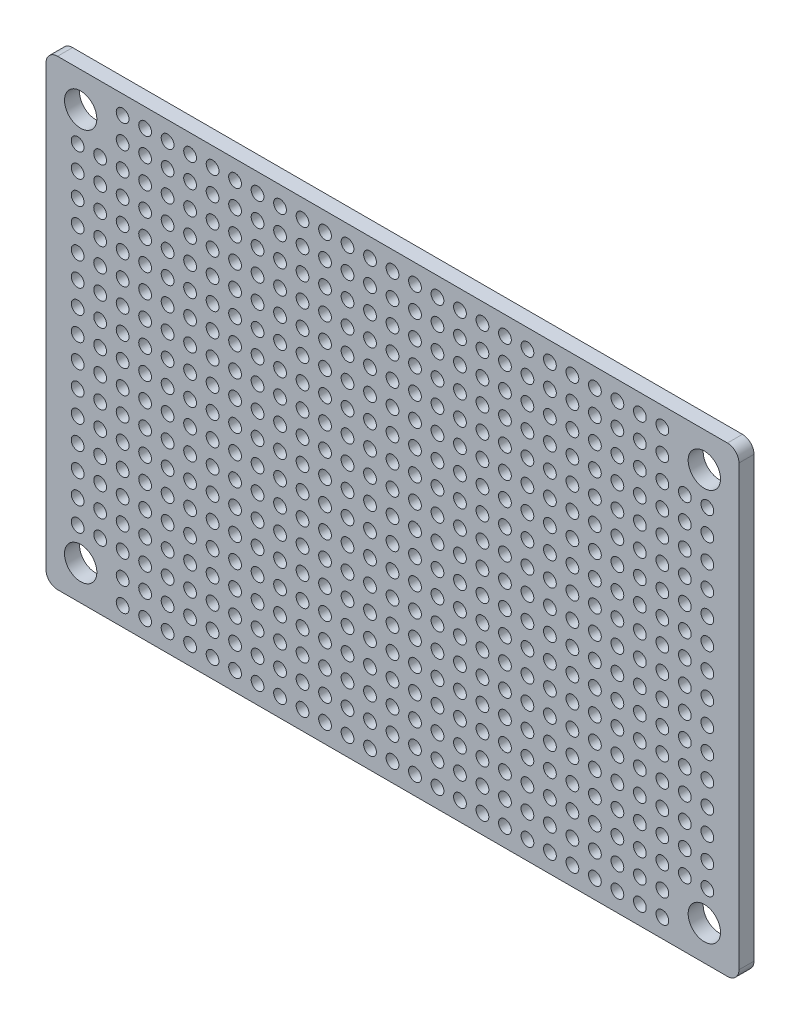
SolidWorks part; units mm, degrees
ref_plane "Front Plane" through (0, 0, 0) normal (0, 0, 1) x (1, 0, 0)
ref_plane "Top Plane" through (0, 0, 0) normal (0, 1, 0) x (1, 0, 0)
ref_plane "Right Plane" through (0, 0, 0) normal (1, 0, 0) x (0, 0, -1)
sketch "Sketch1" plane through (0, 0, 0) normal (0, 0, 1) x (1, 0, 0)
  line L0 (0, 25.4) -> (76.2, 25.4) construction
  line L1 (0, 0) -> (76.2, 0)
  line L2 (0, 0) -> (0, 50.8)
  line L3 (0, 50.8) -> (76.2, 50.8)
  line L4 (76.2, 0) -> (76.2, 50.8)
  line L5 (38.1, 50.8) -> (38.1, 0) construction
  line L6 (4.1421, 48.7367) -> (72.0579, 48.7367) construction
  line L7 (72.39, 2.0633) -> (72.39, 48.7367) construction
  circle A0 centre (3.81, 46.99) radius 1.778
  circle A1 centre (72.39, 46.99) radius 1.778
  circle A2 centre (3.81, 3.81) radius 1.778
  circle A3 centre (72.39, 3.81) radius 1.778
  circle A6 centre (8.4239, 48.7367) radius 0.702
  circle A7 centre (10.8969, 48.7367) radius 0.702
  circle A8 centre (13.3699, 48.7367) radius 0.702
  circle A9 centre (15.8429, 48.7367) radius 0.702
  circle A10 centre (18.3159, 48.7367) radius 0.702
  circle A11 centre (20.7889, 48.7367) radius 0.702
  circle A12 centre (23.2619, 48.7367) radius 0.702
  circle A13 centre (25.7349, 48.7367) radius 0.702
  circle A14 centre (28.208, 48.7367) radius 0.702
  circle A15 centre (30.681, 48.7367) radius 0.702
  circle A16 centre (33.154, 48.7367) radius 0.702
  circle A17 centre (35.627, 48.7367) radius 0.702
  circle A18 centre (38.1, 48.7367) radius 0.702
  circle A19 centre (40.573, 48.7367) radius 0.702
  circle A20 centre (43.046, 48.7367) radius 0.702
  circle A21 centre (45.519, 48.7367) radius 0.702
  circle A22 centre (47.992, 48.7367) radius 0.702
  circle A23 centre (50.4651, 48.7367) radius 0.702
  circle A24 centre (52.9381, 48.7367) radius 0.702
  circle A25 centre (55.4111, 48.7367) radius 0.702
  circle A26 centre (57.8841, 48.7367) radius 0.702
  circle A27 centre (60.3571, 48.7367) radius 0.702
  circle A28 centre (62.8301, 48.7367) radius 0.702
  circle A29 centre (65.3031, 48.7367) radius 0.702
  circle A30 centre (67.7761, 48.7367) radius 0.702
  circle A35 centre (8.4239, 46.1437) radius 0.702
  circle A36 centre (10.8969, 46.1437) radius 0.702
  circle A37 centre (13.3699, 46.1437) radius 0.702
  circle A38 centre (15.8429, 46.1437) radius 0.702
  circle A39 centre (18.3159, 46.1437) radius 0.702
  circle A40 centre (20.7889, 46.1437) radius 0.702
  circle A41 centre (23.2619, 46.1437) radius 0.702
  circle A42 centre (25.7349, 46.1437) radius 0.702
  circle A43 centre (28.208, 46.1437) radius 0.702
  circle A44 centre (30.681, 46.1437) radius 0.702
  circle A45 centre (33.154, 46.1437) radius 0.702
  circle A46 centre (35.627, 46.1437) radius 0.702
  circle A47 centre (38.1, 46.1437) radius 0.702
  circle A48 centre (40.573, 46.1437) radius 0.702
  circle A49 centre (43.046, 46.1437) radius 0.702
  circle A50 centre (45.519, 46.1437) radius 0.702
  circle A51 centre (47.992, 46.1437) radius 0.702
  circle A52 centre (50.4651, 46.1437) radius 0.702
  circle A53 centre (52.9381, 46.1437) radius 0.702
  circle A54 centre (55.4111, 46.1437) radius 0.702
  circle A55 centre (57.8841, 46.1437) radius 0.702
  circle A56 centre (60.3571, 46.1437) radius 0.702
  circle A57 centre (62.8301, 46.1437) radius 0.702
  circle A58 centre (65.3031, 46.1437) radius 0.702
  circle A59 centre (67.7761, 46.1437) radius 0.702
  circle A62 centre (3.4779, 43.5508) radius 0.702
  circle A63 centre (5.9509, 43.5508) radius 0.702
  circle A64 centre (8.4239, 43.5508) radius 0.702
  circle A65 centre (10.8969, 43.5508) radius 0.702
  circle A66 centre (13.3699, 43.5508) radius 0.702
  circle A67 centre (15.8429, 43.5508) radius 0.702
  circle A68 centre (18.3159, 43.5508) radius 0.702
  circle A69 centre (20.7889, 43.5508) radius 0.702
  circle A70 centre (23.2619, 43.5508) radius 0.702
  circle A71 centre (25.7349, 43.5508) radius 0.702
  circle A72 centre (28.208, 43.5508) radius 0.702
  circle A73 centre (30.681, 43.5508) radius 0.702
  circle A74 centre (33.154, 43.5508) radius 0.702
  circle A75 centre (35.627, 43.5508) radius 0.702
  circle A76 centre (38.1, 43.5508) radius 0.702
  circle A77 centre (40.573, 43.5508) radius 0.702
  circle A78 centre (43.046, 43.5508) radius 0.702
  circle A79 centre (45.519, 43.5508) radius 0.702
  circle A80 centre (47.992, 43.5508) radius 0.702
  circle A81 centre (50.4651, 43.5508) radius 0.702
  circle A82 centre (52.9381, 43.5508) radius 0.702
  circle A83 centre (55.4111, 43.5508) radius 0.702
  circle A84 centre (57.8841, 43.5508) radius 0.702
  circle A85 centre (60.3571, 43.5508) radius 0.702
  circle A86 centre (62.8301, 43.5508) radius 0.702
  circle A87 centre (65.3031, 43.5508) radius 0.702
  circle A88 centre (67.7761, 43.5508) radius 0.702
  circle A89 centre (70.2491, 43.5508) radius 0.702
  circle A90 centre (72.7221, 43.5508) radius 0.702
  circle A91 centre (3.4779, 40.9578) radius 0.702
  circle A92 centre (5.9509, 40.9578) radius 0.702
  circle A93 centre (8.4239, 40.9578) radius 0.702
  circle A94 centre (10.8969, 40.9578) radius 0.702
  circle A95 centre (13.3699, 40.9578) radius 0.702
  circle A96 centre (15.8429, 40.9578) radius 0.702
  circle A97 centre (18.3159, 40.9578) radius 0.702
  circle A98 centre (20.7889, 40.9578) radius 0.702
  circle A99 centre (23.2619, 40.9578) radius 0.702
  circle A100 centre (25.7349, 40.9578) radius 0.702
  circle A101 centre (28.208, 40.9578) radius 0.702
  circle A102 centre (30.681, 40.9578) radius 0.702
  circle A103 centre (33.154, 40.9578) radius 0.702
  circle A104 centre (35.627, 40.9578) radius 0.702
  circle A105 centre (38.1, 40.9578) radius 0.702
  circle A106 centre (40.573, 40.9578) radius 0.702
  circle A107 centre (43.046, 40.9578) radius 0.702
  circle A108 centre (45.519, 40.9578) radius 0.702
  circle A109 centre (47.992, 40.9578) radius 0.702
  circle A110 centre (50.4651, 40.9578) radius 0.702
  circle A111 centre (52.9381, 40.9578) radius 0.702
  circle A112 centre (55.4111, 40.9578) radius 0.702
  circle A113 centre (57.8841, 40.9578) radius 0.702
  circle A114 centre (60.3571, 40.9578) radius 0.702
  circle A115 centre (62.8301, 40.9578) radius 0.702
  circle A116 centre (65.3031, 40.9578) radius 0.702
  circle A117 centre (67.7761, 40.9578) radius 0.702
  circle A118 centre (70.2491, 40.9578) radius 0.702
  circle A119 centre (72.7221, 40.9578) radius 0.702
  circle A120 centre (3.4779, 38.3648) radius 0.702
  circle A121 centre (5.9509, 38.3648) radius 0.702
  circle A122 centre (8.4239, 38.3648) radius 0.702
  circle A123 centre (10.8969, 38.3648) radius 0.702
  circle A124 centre (13.3699, 38.3648) radius 0.702
  circle A125 centre (15.8429, 38.3648) radius 0.702
  circle A126 centre (18.3159, 38.3648) radius 0.702
  circle A127 centre (20.7889, 38.3648) radius 0.702
  circle A128 centre (23.2619, 38.3648) radius 0.702
  circle A129 centre (25.7349, 38.3648) radius 0.702
  circle A130 centre (28.208, 38.3648) radius 0.702
  circle A131 centre (30.681, 38.3648) radius 0.702
  circle A132 centre (33.154, 38.3648) radius 0.702
  circle A133 centre (35.627, 38.3648) radius 0.702
  circle A134 centre (38.1, 38.3648) radius 0.702
  circle A135 centre (40.573, 38.3648) radius 0.702
  circle A136 centre (43.046, 38.3648) radius 0.702
  circle A137 centre (45.519, 38.3648) radius 0.702
  circle A138 centre (47.992, 38.3648) radius 0.702
  circle A139 centre (50.4651, 38.3648) radius 0.702
  circle A140 centre (52.9381, 38.3648) radius 0.702
  circle A141 centre (55.4111, 38.3648) radius 0.702
  circle A142 centre (57.8841, 38.3648) radius 0.702
  circle A143 centre (60.3571, 38.3648) radius 0.702
  circle A144 centre (62.8301, 38.3648) radius 0.702
  circle A145 centre (65.3031, 38.3648) radius 0.702
  circle A146 centre (67.7761, 38.3648) radius 0.702
  circle A147 centre (70.2491, 38.3648) radius 0.702
  circle A148 centre (72.7221, 38.3648) radius 0.702
  circle A149 centre (3.4779, 35.7719) radius 0.702
  circle A150 centre (5.9509, 35.7719) radius 0.702
  circle A151 centre (8.4239, 35.7719) radius 0.702
  circle A152 centre (10.8969, 35.7719) radius 0.702
  circle A153 centre (13.3699, 35.7719) radius 0.702
  circle A154 centre (15.8429, 35.7719) radius 0.702
  circle A155 centre (18.3159, 35.7719) radius 0.702
  circle A156 centre (20.7889, 35.7719) radius 0.702
  circle A157 centre (23.2619, 35.7719) radius 0.702
  circle A158 centre (25.7349, 35.7719) radius 0.702
  circle A159 centre (28.208, 35.7719) radius 0.702
  circle A160 centre (30.681, 35.7719) radius 0.702
  circle A161 centre (33.154, 35.7719) radius 0.702
  circle A162 centre (35.627, 35.7719) radius 0.702
  circle A163 centre (38.1, 35.7719) radius 0.702
  circle A164 centre (40.573, 35.7719) radius 0.702
  circle A165 centre (43.046, 35.7719) radius 0.702
  circle A166 centre (45.519, 35.7719) radius 0.702
  circle A167 centre (47.992, 35.7719) radius 0.702
  circle A168 centre (50.4651, 35.7719) radius 0.702
  circle A169 centre (52.9381, 35.7719) radius 0.702
  circle A170 centre (55.4111, 35.7719) radius 0.702
  circle A171 centre (57.8841, 35.7719) radius 0.702
  circle A172 centre (60.3571, 35.7719) radius 0.702
  circle A173 centre (62.8301, 35.7719) radius 0.702
  circle A174 centre (65.3031, 35.7719) radius 0.702
  circle A175 centre (67.7761, 35.7719) radius 0.702
  circle A176 centre (70.2491, 35.7719) radius 0.702
  circle A177 centre (72.7221, 35.7719) radius 0.702
  circle A178 centre (3.4779, 33.1789) radius 0.702
  circle A179 centre (5.9509, 33.1789) radius 0.702
  circle A180 centre (8.4239, 33.1789) radius 0.702
  circle A181 centre (10.8969, 33.1789) radius 0.702
  circle A182 centre (13.3699, 33.1789) radius 0.702
  circle A183 centre (15.8429, 33.1789) radius 0.702
  circle A184 centre (18.3159, 33.1789) radius 0.702
  circle A185 centre (20.7889, 33.1789) radius 0.702
  circle A186 centre (23.2619, 33.1789) radius 0.702
  circle A187 centre (25.7349, 33.1789) radius 0.702
  circle A188 centre (28.208, 33.1789) radius 0.702
  circle A189 centre (30.681, 33.1789) radius 0.702
  circle A190 centre (33.154, 33.1789) radius 0.702
  circle A191 centre (35.627, 33.1789) radius 0.702
  circle A192 centre (38.1, 33.1789) radius 0.702
  circle A193 centre (40.573, 33.1789) radius 0.702
  circle A194 centre (43.046, 33.1789) radius 0.702
  circle A195 centre (45.519, 33.1789) radius 0.702
  circle A196 centre (47.992, 33.1789) radius 0.702
  circle A197 centre (50.4651, 33.1789) radius 0.702
  circle A198 centre (52.9381, 33.1789) radius 0.702
  circle A199 centre (55.4111, 33.1789) radius 0.702
  circle A200 centre (57.8841, 33.1789) radius 0.702
  circle A201 centre (60.3571, 33.1789) radius 0.702
  circle A202 centre (62.8301, 33.1789) radius 0.702
  circle A203 centre (65.3031, 33.1789) radius 0.702
  circle A204 centre (67.7761, 33.1789) radius 0.702
  circle A205 centre (70.2491, 33.1789) radius 0.702
  circle A206 centre (72.7221, 33.1789) radius 0.702
  circle A207 centre (3.4779, 30.5859) radius 0.702
  circle A208 centre (5.9509, 30.5859) radius 0.702
  circle A209 centre (8.4239, 30.5859) radius 0.702
  circle A210 centre (10.8969, 30.5859) radius 0.702
  circle A211 centre (13.3699, 30.5859) radius 0.702
  circle A212 centre (15.8429, 30.5859) radius 0.702
  circle A213 centre (18.3159, 30.5859) radius 0.702
  circle A214 centre (20.7889, 30.5859) radius 0.702
  circle A215 centre (23.2619, 30.5859) radius 0.702
  circle A216 centre (25.7349, 30.5859) radius 0.702
  circle A217 centre (28.208, 30.5859) radius 0.702
  circle A218 centre (30.681, 30.5859) radius 0.702
  circle A219 centre (33.154, 30.5859) radius 0.702
  circle A220 centre (35.627, 30.5859) radius 0.702
  circle A221 centre (38.1, 30.5859) radius 0.702
  circle A222 centre (40.573, 30.5859) radius 0.702
  circle A223 centre (43.046, 30.5859) radius 0.702
  circle A224 centre (45.519, 30.5859) radius 0.702
  circle A225 centre (47.992, 30.5859) radius 0.702
  circle A226 centre (50.4651, 30.5859) radius 0.702
  circle A227 centre (52.9381, 30.5859) radius 0.702
  circle A228 centre (55.4111, 30.5859) radius 0.702
  circle A229 centre (57.8841, 30.5859) radius 0.702
  circle A230 centre (60.3571, 30.5859) radius 0.702
  circle A231 centre (62.8301, 30.5859) radius 0.702
  circle A232 centre (65.3031, 30.5859) radius 0.702
  circle A233 centre (67.7761, 30.5859) radius 0.702
  circle A234 centre (70.2491, 30.5859) radius 0.702
  circle A235 centre (72.7221, 30.5859) radius 0.702
  circle A236 centre (3.4779, 27.993) radius 0.702
  circle A237 centre (5.9509, 27.993) radius 0.702
  circle A238 centre (8.4239, 27.993) radius 0.702
  circle A239 centre (10.8969, 27.993) radius 0.702
  circle A240 centre (13.3699, 27.993) radius 0.702
  circle A241 centre (15.8429, 27.993) radius 0.702
  circle A242 centre (18.3159, 27.993) radius 0.702
  circle A243 centre (20.7889, 27.993) radius 0.702
  circle A244 centre (23.2619, 27.993) radius 0.702
  circle A245 centre (25.7349, 27.993) radius 0.702
  circle A246 centre (28.208, 27.993) radius 0.702
  circle A247 centre (30.681, 27.993) radius 0.702
  circle A248 centre (33.154, 27.993) radius 0.702
  circle A249 centre (35.627, 27.993) radius 0.702
  circle A250 centre (38.1, 27.993) radius 0.702
  circle A251 centre (40.573, 27.993) radius 0.702
  circle A252 centre (43.046, 27.993) radius 0.702
  circle A253 centre (45.519, 27.993) radius 0.702
  circle A254 centre (47.992, 27.993) radius 0.702
  circle A255 centre (50.4651, 27.993) radius 0.702
  circle A256 centre (52.9381, 27.993) radius 0.702
  circle A257 centre (55.4111, 27.993) radius 0.702
  circle A258 centre (57.8841, 27.993) radius 0.702
  circle A259 centre (60.3571, 27.993) radius 0.702
  circle A260 centre (62.8301, 27.993) radius 0.702
  circle A261 centre (65.3031, 27.993) radius 0.702
  circle A262 centre (67.7761, 27.993) radius 0.702
  circle A263 centre (70.2491, 27.993) radius 0.702
  circle A264 centre (72.7221, 27.993) radius 0.702
  circle A265 centre (3.4779, 25.4) radius 0.702
  circle A266 centre (5.9509, 25.4) radius 0.702
  circle A267 centre (8.4239, 25.4) radius 0.702
  circle A268 centre (10.8969, 25.4) radius 0.702
  circle A269 centre (13.3699, 25.4) radius 0.702
  circle A270 centre (15.8429, 25.4) radius 0.702
  circle A271 centre (18.3159, 25.4) radius 0.702
  circle A272 centre (20.7889, 25.4) radius 0.702
  circle A273 centre (23.2619, 25.4) radius 0.702
  circle A274 centre (25.7349, 25.4) radius 0.702
  circle A275 centre (28.208, 25.4) radius 0.702
  circle A276 centre (30.681, 25.4) radius 0.702
  circle A277 centre (33.154, 25.4) radius 0.702
  circle A278 centre (35.627, 25.4) radius 0.702
  circle A279 centre (38.1, 25.4) radius 0.702
  circle A280 centre (40.573, 25.4) radius 0.702
  circle A281 centre (43.046, 25.4) radius 0.702
  circle A282 centre (45.519, 25.4) radius 0.702
  circle A283 centre (47.992, 25.4) radius 0.702
  circle A284 centre (50.4651, 25.4) radius 0.702
  circle A285 centre (52.9381, 25.4) radius 0.702
  circle A286 centre (55.4111, 25.4) radius 0.702
  circle A287 centre (57.8841, 25.4) radius 0.702
  circle A288 centre (60.3571, 25.4) radius 0.702
  circle A289 centre (62.8301, 25.4) radius 0.702
  circle A290 centre (65.3031, 25.4) radius 0.702
  circle A291 centre (67.7761, 25.4) radius 0.702
  circle A292 centre (70.2491, 25.4) radius 0.702
  circle A293 centre (72.7221, 25.4) radius 0.702
  circle A294 centre (3.4779, 22.807) radius 0.702
  circle A295 centre (5.9509, 22.807) radius 0.702
  circle A296 centre (8.4239, 22.807) radius 0.702
  circle A297 centre (10.8969, 22.807) radius 0.702
  circle A298 centre (13.3699, 22.807) radius 0.702
  circle A299 centre (15.8429, 22.807) radius 0.702
  circle A300 centre (18.3159, 22.807) radius 0.702
  circle A301 centre (20.7889, 22.807) radius 0.702
  circle A302 centre (23.2619, 22.807) radius 0.702
  circle A303 centre (25.7349, 22.807) radius 0.702
  circle A304 centre (28.208, 22.807) radius 0.702
  circle A305 centre (30.681, 22.807) radius 0.702
  circle A306 centre (33.154, 22.807) radius 0.702
  circle A307 centre (35.627, 22.807) radius 0.702
  circle A308 centre (38.1, 22.807) radius 0.702
  circle A309 centre (40.573, 22.807) radius 0.702
  circle A310 centre (43.046, 22.807) radius 0.702
  circle A311 centre (45.519, 22.807) radius 0.702
  circle A312 centre (47.992, 22.807) radius 0.702
  circle A313 centre (50.4651, 22.807) radius 0.702
  circle A314 centre (52.9381, 22.807) radius 0.702
  circle A315 centre (55.4111, 22.807) radius 0.702
  circle A316 centre (57.8841, 22.807) radius 0.702
  circle A317 centre (60.3571, 22.807) radius 0.702
  circle A318 centre (62.8301, 22.807) radius 0.702
  circle A319 centre (65.3031, 22.807) radius 0.702
  circle A320 centre (67.7761, 22.807) radius 0.702
  circle A321 centre (70.2491, 22.807) radius 0.702
  circle A322 centre (72.7221, 22.807) radius 0.702
  circle A323 centre (3.4779, 20.2141) radius 0.702
  circle A324 centre (5.9509, 20.2141) radius 0.702
  circle A325 centre (8.4239, 20.2141) radius 0.702
  circle A326 centre (10.8969, 20.2141) radius 0.702
  circle A327 centre (13.3699, 20.2141) radius 0.702
  circle A328 centre (15.8429, 20.2141) radius 0.702
  circle A329 centre (18.3159, 20.2141) radius 0.702
  circle A330 centre (20.7889, 20.2141) radius 0.702
  circle A331 centre (23.2619, 20.2141) radius 0.702
  circle A332 centre (25.7349, 20.2141) radius 0.702
  circle A333 centre (28.208, 20.2141) radius 0.702
  circle A334 centre (30.681, 20.2141) radius 0.702
  circle A335 centre (33.154, 20.2141) radius 0.702
  circle A336 centre (35.627, 20.2141) radius 0.702
  circle A337 centre (38.1, 20.2141) radius 0.702
  circle A338 centre (40.573, 20.2141) radius 0.702
  circle A339 centre (43.046, 20.2141) radius 0.702
  circle A340 centre (45.519, 20.2141) radius 0.702
  circle A341 centre (47.992, 20.2141) radius 0.702
  circle A342 centre (50.4651, 20.2141) radius 0.702
  circle A343 centre (52.9381, 20.2141) radius 0.702
  circle A344 centre (55.4111, 20.2141) radius 0.702
  circle A345 centre (57.8841, 20.2141) radius 0.702
  circle A346 centre (60.3571, 20.2141) radius 0.702
  circle A347 centre (62.8301, 20.2141) radius 0.702
  circle A348 centre (65.3031, 20.2141) radius 0.702
  circle A349 centre (67.7761, 20.2141) radius 0.702
  circle A350 centre (70.2491, 20.2141) radius 0.702
  circle A351 centre (72.7221, 20.2141) radius 0.702
  circle A352 centre (3.4779, 17.6211) radius 0.702
  circle A353 centre (5.9509, 17.6211) radius 0.702
  circle A354 centre (8.4239, 17.6211) radius 0.702
  circle A355 centre (10.8969, 17.6211) radius 0.702
  circle A356 centre (13.3699, 17.6211) radius 0.702
  circle A357 centre (15.8429, 17.6211) radius 0.702
  circle A358 centre (18.3159, 17.6211) radius 0.702
  circle A359 centre (20.7889, 17.6211) radius 0.702
  circle A360 centre (23.2619, 17.6211) radius 0.702
  circle A361 centre (25.7349, 17.6211) radius 0.702
  circle A362 centre (28.208, 17.6211) radius 0.702
  circle A363 centre (30.681, 17.6211) radius 0.702
  circle A364 centre (33.154, 17.6211) radius 0.702
  circle A365 centre (35.627, 17.6211) radius 0.702
  circle A366 centre (38.1, 17.6211) radius 0.702
  circle A367 centre (40.573, 17.6211) radius 0.702
  circle A368 centre (43.046, 17.6211) radius 0.702
  circle A369 centre (45.519, 17.6211) radius 0.702
  circle A370 centre (47.992, 17.6211) radius 0.702
  circle A371 centre (50.4651, 17.6211) radius 0.702
  circle A372 centre (52.9381, 17.6211) radius 0.702
  circle A373 centre (55.4111, 17.6211) radius 0.702
  circle A374 centre (57.8841, 17.6211) radius 0.702
  circle A375 centre (60.3571, 17.6211) radius 0.702
  circle A376 centre (62.8301, 17.6211) radius 0.702
  circle A377 centre (65.3031, 17.6211) radius 0.702
  circle A378 centre (67.7761, 17.6211) radius 0.702
  circle A379 centre (70.2491, 17.6211) radius 0.702
  circle A380 centre (72.7221, 17.6211) radius 0.702
  circle A381 centre (3.4779, 15.0281) radius 0.702
  circle A382 centre (5.9509, 15.0281) radius 0.702
  circle A383 centre (8.4239, 15.0281) radius 0.702
  circle A384 centre (10.8969, 15.0281) radius 0.702
  circle A385 centre (13.3699, 15.0281) radius 0.702
  circle A386 centre (15.8429, 15.0281) radius 0.702
  circle A387 centre (18.3159, 15.0281) radius 0.702
  circle A388 centre (20.7889, 15.0281) radius 0.702
  circle A389 centre (23.2619, 15.0281) radius 0.702
  circle A390 centre (25.7349, 15.0281) radius 0.702
  circle A391 centre (28.208, 15.0281) radius 0.702
  circle A392 centre (30.681, 15.0281) radius 0.702
  circle A393 centre (33.154, 15.0281) radius 0.702
  circle A394 centre (35.627, 15.0281) radius 0.702
  circle A395 centre (38.1, 15.0281) radius 0.702
  circle A396 centre (40.573, 15.0281) radius 0.702
  circle A397 centre (43.046, 15.0281) radius 0.702
  circle A398 centre (45.519, 15.0281) radius 0.702
  circle A399 centre (47.992, 15.0281) radius 0.702
  circle A400 centre (50.4651, 15.0281) radius 0.702
  circle A401 centre (52.9381, 15.0281) radius 0.702
  circle A402 centre (55.4111, 15.0281) radius 0.702
  circle A403 centre (57.8841, 15.0281) radius 0.702
  circle A404 centre (60.3571, 15.0281) radius 0.702
  circle A405 centre (62.8301, 15.0281) radius 0.702
  circle A406 centre (65.3031, 15.0281) radius 0.702
  circle A407 centre (67.7761, 15.0281) radius 0.702
  circle A408 centre (70.2491, 15.0281) radius 0.702
  circle A409 centre (72.7221, 15.0281) radius 0.702
  circle A410 centre (3.4779, 12.4352) radius 0.702
  circle A411 centre (5.9509, 12.4352) radius 0.702
  circle A412 centre (8.4239, 12.4352) radius 0.702
  circle A413 centre (10.8969, 12.4352) radius 0.702
  circle A414 centre (13.3699, 12.4352) radius 0.702
  circle A415 centre (15.8429, 12.4352) radius 0.702
  circle A416 centre (18.3159, 12.4352) radius 0.702
  circle A417 centre (20.7889, 12.4352) radius 0.702
  circle A418 centre (23.2619, 12.4352) radius 0.702
  circle A419 centre (25.7349, 12.4352) radius 0.702
  circle A420 centre (28.208, 12.4352) radius 0.702
  circle A421 centre (30.681, 12.4352) radius 0.702
  circle A422 centre (33.154, 12.4352) radius 0.702
  circle A423 centre (35.627, 12.4352) radius 0.702
  circle A424 centre (38.1, 12.4352) radius 0.702
  circle A425 centre (40.573, 12.4352) radius 0.702
  circle A426 centre (43.046, 12.4352) radius 0.702
  circle A427 centre (45.519, 12.4352) radius 0.702
  circle A428 centre (47.992, 12.4352) radius 0.702
  circle A429 centre (50.4651, 12.4352) radius 0.702
  circle A430 centre (52.9381, 12.4352) radius 0.702
  circle A431 centre (55.4111, 12.4352) radius 0.702
  circle A432 centre (57.8841, 12.4352) radius 0.702
  circle A433 centre (60.3571, 12.4352) radius 0.702
  circle A434 centre (62.8301, 12.4352) radius 0.702
  circle A435 centre (65.3031, 12.4352) radius 0.702
  circle A436 centre (67.7761, 12.4352) radius 0.702
  circle A437 centre (70.2491, 12.4352) radius 0.702
  circle A438 centre (72.7221, 12.4352) radius 0.702
  circle A439 centre (3.4779, 9.8422) radius 0.702
  circle A440 centre (5.9509, 9.8422) radius 0.702
  circle A441 centre (8.4239, 9.8422) radius 0.702
  circle A442 centre (10.8969, 9.8422) radius 0.702
  circle A443 centre (13.3699, 9.8422) radius 0.702
  circle A444 centre (15.8429, 9.8422) radius 0.702
  circle A445 centre (18.3159, 9.8422) radius 0.702
  circle A446 centre (20.7889, 9.8422) radius 0.702
  circle A447 centre (23.2619, 9.8422) radius 0.702
  circle A448 centre (25.7349, 9.8422) radius 0.702
  circle A449 centre (28.208, 9.8422) radius 0.702
  circle A450 centre (30.681, 9.8422) radius 0.702
  circle A451 centre (33.154, 9.8422) radius 0.702
  circle A452 centre (35.627, 9.8422) radius 0.702
  circle A453 centre (38.1, 9.8422) radius 0.702
  circle A454 centre (40.573, 9.8422) radius 0.702
  circle A455 centre (43.046, 9.8422) radius 0.702
  circle A456 centre (45.519, 9.8422) radius 0.702
  circle A457 centre (47.992, 9.8422) radius 0.702
  circle A458 centre (50.4651, 9.8422) radius 0.702
  circle A459 centre (52.9381, 9.8422) radius 0.702
  circle A460 centre (55.4111, 9.8422) radius 0.702
  circle A461 centre (57.8841, 9.8422) radius 0.702
  circle A462 centre (60.3571, 9.8422) radius 0.702
  circle A463 centre (62.8301, 9.8422) radius 0.702
  circle A464 centre (65.3031, 9.8422) radius 0.702
  circle A465 centre (67.7761, 9.8422) radius 0.702
  circle A466 centre (70.2491, 9.8422) radius 0.702
  circle A467 centre (72.7221, 9.8422) radius 0.702
  circle A468 centre (3.4779, 7.2492) radius 0.702
  circle A469 centre (5.9509, 7.2492) radius 0.702
  circle A470 centre (8.4239, 7.2492) radius 0.702
  circle A471 centre (10.8969, 7.2492) radius 0.702
  circle A472 centre (13.3699, 7.2492) radius 0.702
  circle A473 centre (15.8429, 7.2492) radius 0.702
  circle A474 centre (18.3159, 7.2492) radius 0.702
  circle A475 centre (20.7889, 7.2492) radius 0.702
  circle A476 centre (23.2619, 7.2492) radius 0.702
  circle A477 centre (25.7349, 7.2492) radius 0.702
  circle A478 centre (28.208, 7.2492) radius 0.702
  circle A479 centre (30.681, 7.2492) radius 0.702
  circle A480 centre (33.154, 7.2492) radius 0.702
  circle A481 centre (35.627, 7.2492) radius 0.702
  circle A482 centre (38.1, 7.2492) radius 0.702
  circle A483 centre (40.573, 7.2492) radius 0.702
  circle A484 centre (43.046, 7.2492) radius 0.702
  circle A485 centre (45.519, 7.2492) radius 0.702
  circle A486 centre (47.992, 7.2492) radius 0.702
  circle A487 centre (50.4651, 7.2492) radius 0.702
  circle A488 centre (52.9381, 7.2492) radius 0.702
  circle A489 centre (55.4111, 7.2492) radius 0.702
  circle A490 centre (57.8841, 7.2492) radius 0.702
  circle A491 centre (60.3571, 7.2492) radius 0.702
  circle A492 centre (62.8301, 7.2492) radius 0.702
  circle A493 centre (65.3031, 7.2492) radius 0.702
  circle A494 centre (67.7761, 7.2492) radius 0.702
  circle A495 centre (70.2491, 7.2492) radius 0.702
  circle A496 centre (72.7221, 7.2492) radius 0.702
  circle A499 centre (8.4239, 4.6563) radius 0.702
  circle A500 centre (10.8969, 4.6563) radius 0.702
  circle A501 centre (13.3699, 4.6563) radius 0.702
  circle A502 centre (15.8429, 4.6563) radius 0.702
  circle A503 centre (18.3159, 4.6563) radius 0.702
  circle A504 centre (20.7889, 4.6563) radius 0.702
  circle A505 centre (23.2619, 4.6563) radius 0.702
  circle A506 centre (25.7349, 4.6563) radius 0.702
  circle A507 centre (28.208, 4.6563) radius 0.702
  circle A508 centre (30.681, 4.6563) radius 0.702
  circle A509 centre (33.154, 4.6563) radius 0.702
  circle A510 centre (35.627, 4.6563) radius 0.702
  circle A511 centre (38.1, 4.6563) radius 0.702
  circle A512 centre (40.573, 4.6563) radius 0.702
  circle A513 centre (43.046, 4.6563) radius 0.702
  circle A514 centre (45.519, 4.6563) radius 0.702
  circle A515 centre (47.992, 4.6563) radius 0.702
  circle A516 centre (50.4651, 4.6563) radius 0.702
  circle A517 centre (52.9381, 4.6563) radius 0.702
  circle A518 centre (55.4111, 4.6563) radius 0.702
  circle A519 centre (57.8841, 4.6563) radius 0.702
  circle A520 centre (60.3571, 4.6563) radius 0.702
  circle A521 centre (62.8301, 4.6563) radius 0.702
  circle A522 centre (65.3031, 4.6563) radius 0.702
  circle A523 centre (67.7761, 4.6563) radius 0.702
  circle A528 centre (8.4239, 2.0633) radius 0.702
  circle A529 centre (10.8969, 2.0633) radius 0.702
  circle A530 centre (13.3699, 2.0633) radius 0.702
  circle A531 centre (15.8429, 2.0633) radius 0.702
  circle A532 centre (18.3159, 2.0633) radius 0.702
  circle A533 centre (20.7889, 2.0633) radius 0.702
  circle A534 centre (23.2619, 2.0633) radius 0.702
  circle A535 centre (25.7349, 2.0633) radius 0.702
  circle A536 centre (28.208, 2.0633) radius 0.702
  circle A537 centre (30.681, 2.0633) radius 0.702
  circle A538 centre (33.154, 2.0633) radius 0.702
  circle A539 centre (35.627, 2.0633) radius 0.702
  circle A540 centre (38.1, 2.0633) radius 0.702
  circle A541 centre (40.573, 2.0633) radius 0.702
  circle A542 centre (43.046, 2.0633) radius 0.702
  circle A543 centre (45.519, 2.0633) radius 0.702
  circle A544 centre (47.992, 2.0633) radius 0.702
  circle A545 centre (50.4651, 2.0633) radius 0.702
  circle A546 centre (52.9381, 2.0633) radius 0.702
  circle A547 centre (55.4111, 2.0633) radius 0.702
  circle A548 centre (57.8841, 2.0633) radius 0.702
  circle A549 centre (60.3571, 2.0633) radius 0.702
  circle A550 centre (62.8301, 2.0633) radius 0.702
  circle A551 centre (65.3031, 2.0633) radius 0.702
  circle A552 centre (67.7761, 2.0633) radius 0.702
  circle A555 centre (3.4779, 46.1437) radius 0.702 [skipped]
  arc A556 (5.5693, 46.733) -> (5.2696, 45.9746) centre (5.9509, 46.1437) ccw [skipped]
  arc A557 (5.2489, 48.7367) -> (6.6528, 48.7367) centre (5.9509, 48.7367) ccw [skipped]
  arc A558 (69.5472, 48.7367) -> (70.9511, 48.7367) centre (70.2491, 48.7367) ccw [skipped]
  arc A559 (72.7221, 46.8457) -> (72.7221, 45.4418) centre (72.7221, 46.1437) ccw [skipped]
  arc A560 (70.9304, 45.9746) -> (70.6307, 46.733) centre (70.2491, 46.1437) ccw [skipped]
  circle A561 centre (70.2491, 2.0633) radius 0.702 [skipped]
  arc A562 (72.7221, 3.9543) -> (72.7221, 5.3582) centre (72.7221, 4.6563) ccw [skipped]
  arc A563 (70.6307, 4.067) -> (70.9304, 4.8254) centre (70.2491, 4.6563) ccw [skipped]
  arc A564 (72.7221, 2.7653) -> (72.0202, 2.0709) centre (72.7221, 2.0633) ccw [skipped]
  circle A565 centre (3.4779, 4.6563) radius 0.702 [skipped]
  circle A566 centre (5.9509, 2.0633) radius 0.702 [skipped]
  arc A567 (4.1798, 2.0709) -> (2.8277, 2.328) centre (3.4779, 2.0633) ccw [skipped]
  arc A568 (5.2696, 4.8254) -> (5.5693, 4.067) centre (5.9509, 4.6563) ccw [skipped]
  arc A569 (4.1798, 48.7291) -> (4.1798, 48.7367) centre (3.4779, 48.7367) ccw [skipped]
  arc A570 (72.0202, 48.7367) -> (72.0202, 48.7291) centre (72.7221, 48.7367) ccw [skipped]
  circle A571 centre (3.81, 3.81) radius 1.778 [skipped]
  dimension "D3" = 3.556
  dimension "D1" = 50.8
  dimension "D2" = 76.2
  dimension "D4" = 3.81
  dimension "D5" = 3.81
  dimension "D6" = 2
  dimension "D7" = 2
  dimension "D8" = 29
  dimension "D9" = 19
extrude "Boss-Extrude1" add sketch "Sketch1" along normal blind 1.651
fillet "Fillet1" radius 1.27 4 edges at (0, 50.8, 0.8255) (0, 0, 0.8255) (76.2, 0, 0.8255) (76.2, 50.8, 0.8255)
ref_plane "Plane1" through (0, 25.4, 0) normal (0, -1, 0) x (1, 0, 0)
ref_plane "Plane2" through (38.1, 0, 0) normal (1, 0, 0) x (0, 0, -1)
